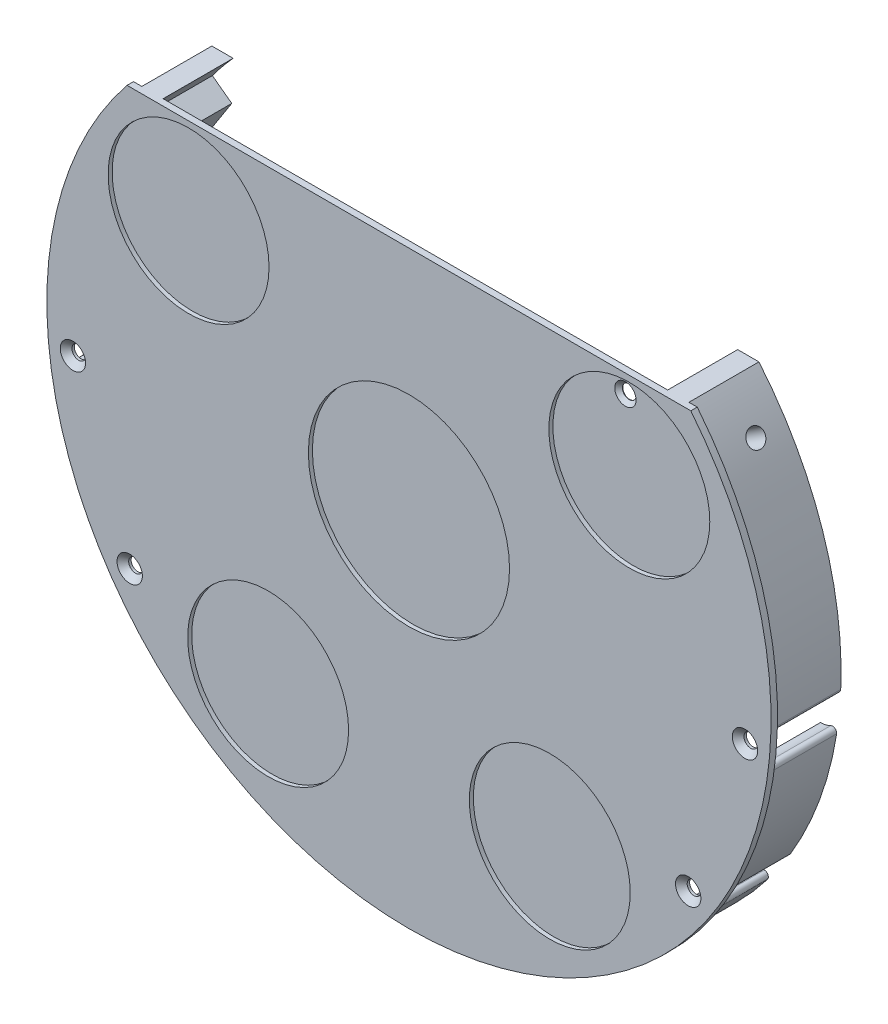
SolidWorks part; units mm, degrees
ref_plane "Front Plane" through (0, 0, 0) normal (0, 0, 1) x (1, 0, 0)
ref_plane "Top Plane" through (0, 0, 0) normal (0, 1, 0) x (1, 0, 0)
ref_plane "Right Plane" through (0, 0, 0) normal (1, 0, 0) x (0, 0, -1)
sketch "Sketch1" plane through (0, 0, 0) normal (0, 0, 1) x (1, 0, 0)
  line L0 (-70.0553, 56.5) -> (70.0553, 56.5)
  line L1 (-68.1175, 56.5) -> (68.1175, 56.5)
  arc A0 (70.0553, 56.5) -> (-70.0553, 56.5) centre (0, 0) cw
  circle A1 centre (52.8, 51) radius 1.7 construction
  circle A2 centre (-69.4053, -47.2163) radius 1.7 construction
  circle A3 centre (-83.5176, -8.4431) radius 1.7 construction
  circle A4 centre (69.4053, -47.2163) radius 1.7 construction
  circle A5 centre (83.5176, -8.4431) radius 1.7 construction
  arc A6 (68.1175, 56.5) -> (-68.1175, 56.5) centre (0, 0) cw construction
  circle A7 centre (-83.5176, -8.4431) radius 1.7
  circle A8 centre (-69.4053, -47.2163) radius 1.7
  circle A9 centre (52.8, 51) radius 1.7
  circle A10 centre (83.5176, -8.4431) radius 1.7
  circle A11 centre (69.4053, -47.2163) radius 1.7
  point P20 (-83.5176, -8.4431)
  point P21 (-69.4053, -47.2163)
  point P22 (52.8, 51)
  point P23 (83.5176, -8.4431)
  point P24 (69.4053, -47.2163)
  point P25 (0, 56.5)
  dimension "D2" = 90
  dimension "D3" = 88.5
  dimension "D15" = 3.4
  dimension "D1" = 140.1107
  dimension "D4" = 136.2351
  dimension "D5" = 64.9431
  dimension "D6" = 105.796
  dimension "D7" = 103.7163
  dimension "D8" = 124.7965
  dimension "D9" = 124.7965
  dimension "D10" = 103.7163
  dimension "D11" = 105.796
  dimension "D12" = 64.9431
  dimension "D13" = 53.0857
  dimension "D14" = 5.5
extrude "Boss-Extrude1" add sketch "Sketch1" along normal blind 2 contours A0 L0 A11 A10 A9 A8 A7 region at (-0.0217, -10.331, 0)
sketch "Sketch3" plane through (0, 0, 2) normal (0, 0, 1) x (1, 0, 0)
  line L0 (-70.0553, 56.5) -> (70.0553, 56.5)
  arc A0 (70.0553, 56.5) -> (-70.0553, 56.5) centre (0, 0) cw
  circle A1 centre (-54.772, 35) radius 20
  circle A2 centre (0, 0) radius 25
  circle A3 centre (54.7723, 35) radius 20
  circle A4 centre (35.0004, -54.772) radius 20
  circle A5 centre (-35, -54.7723) radius 20
  circle M3 centre (52.8, 51) radius 1.7
  dimension "D1" = 90
  dimension "D2" = 40
  dimension "D3" = 50
extrude "Cut-Extrude1" cut sketch "Sketch3" against normal blind 0.5 contours A1 | A5 | A2 | A4 | A3 M3 region at (-54.772, 35, 2) region at (0, 0, 2) region at (54.7866, 34.8836, 2) region at (35.0004, -54.772, 2) region at (-35, -54.7723, 2)
sketch "Sketch4" plane through (0, 0, 0) normal (0, 0, -1) x (-1, 0, 0)
  circle A0 centre (-52.8, 51) radius 3
  circle A1 centre (-83.5176, -8.4431) radius 3
  circle A2 centre (-69.4053, -47.2163) radius 3
  circle A3 centre (69.4053, -47.2163) radius 3
  circle A4 centre (83.5176, -8.4431) radius 3
  arc M6 (-70.0553, 56.5) -> (70.0553, 56.5) centre (0, 0) ccw
  line M7 (70.0553, 56.5) -> (-70.0553, 56.5)
  dimension "D1" = 6
  dimension "D2" = 6
extrude "Boss-Extrude2" add sketch "Sketch4" along normal blind 2 contours A4 A3 A2 A1 A0 M7 M6 region at (-0.0677, -10.3234, 0)
sketch "Sketch5" plane through (0, 0, -2) normal (0, 0, -1) x (-1, 0, 0)
  line L0 (70.0553, 56.5) -> (-70.0553, 56.5) construction
  line L1 (-67.9876, 56.5) -> (-62.6986, 56.5)
  line L2 (62.6986, 56.5) -> (67.9876, 56.5)
  line L3 (0, 0) -> (0, 20.6116) construction
  arc A0 (-67.9876, 56.5) -> (67.9876, 56.5) centre (0, 0) ccw
  arc A1 (-62.6986, 56.5) -> (62.6986, 56.5) centre (0, 0) ccw
  arc A2 (-88.1552, -6.5742) -> (-84.327, -3.5091) centre (-83.5176, -8.4431) cw
  arc A3 (-87.6873, -11.2023) -> (-83.3231, -13.4393) centre (-83.5176, -8.4431) ccw
  arc A4 (-74.3731, -47.7828) -> (-72.4679, -43.264) centre (-69.4053, -47.2163) cw
  arc A5 (-71.7566, -51.6289) -> (-66.8538, -51.5163) centre (-69.4053, -47.2163) ccw
  arc A6 (88.1552, -6.5742) -> (84.327, -3.5091) centre (83.5176, -8.4431) ccw
  arc A7 (71.7566, -51.6289) -> (66.8538, -51.5163) centre (69.4053, -47.2163) cw
  arc A8 (74.3731, -47.7828) -> (72.4679, -43.264) centre (69.4053, -47.2163) ccw
  arc A9 (87.6873, -11.2023) -> (83.3231, -13.4393) centre (83.5176, -8.4431) cw
  line M8 (70.0553, 56.5) -> (-70.0553, 56.5)
  dimension "D2" = 5
  dimension "D3" = 5
  dimension "D4" = 5
  dimension "D5" = 5
  dimension "D1" = 88.4
  dimension "D6" = 84.4
extrude "Boss-Extrude3" add sketch "Sketch5" along normal blind 15 contours A0 A2 A1 M8 | A0 A4 A1 A3 | A0 L3 A1 A5 | L3 A0 A7 A1 | A0 A9 A1 A8 | A6 A0 A1 M8 region at (65.3431, 55.8189, -2) region at (-65.3431, 55.8189, -2) region at (80.7079, -29.3753, -2) region at (-80.7079, -29.3753, -2) region at (69.2564, -53.6963, -2)
fillet "Fillet1" radius 1 8 edges at (-88.1552, -6.5742, -9.5) (-87.6873, -11.2023, -9.5) (-74.3731, -47.7828, -9.5) (-71.7566, -51.6289, -9.5) (74.3731, -47.7828, -9.5) (71.7566, -51.6289, -9.5) (88.1552, -6.5742, -9.5) (87.6873, -11.2023, -9.5)
sketch "Sketch6" plane through (0, 0, -17) normal (0, 0, -1) x (-1, 0, 0)
  line L0 (-71.0732, 52.5657) -> (-63.0333, 46.6194)
  line L1 (-77.3412, 42.8124) -> (-69.3012, 36.866)
  line L2 (-69.3012, 36.866) -> (-63.0333, 46.6194)
  line L3 (-77.3412, 42.8124) -> (-71.0732, 52.5657) construction
  line L4 (0, 56.5) -> (0, 0) construction
  line L5 (62.6986, 56.5) -> (-62.6986, 56.5) construction
  line L6 (69.3012, 36.866) -> (63.0333, 46.6194)
  line L7 (77.3412, 42.8124) -> (69.3012, 36.866)
  line L8 (71.0732, 52.5657) -> (63.0333, 46.6194)
  arc A0 (-67.9876, 56.5) -> (-71.0732, 52.5657) centre (0, 0) ccw
  arc A1 (-71.0732, 52.5657) -> (-77.3412, 42.8124) centre (0, 0) ccw
  arc A2 (71.0732, 52.5657) -> (77.3412, 42.8124) centre (0, 0) cw
  point P7 (-74.3673, 47.7919)
  arc M9 (-84.327, -3.5091) -> (-62.6986, 56.5) centre (0, 0) cw
  dimension "D1" = 5
  dimension "D2" = 5.8
  dimension "D3" = 10
extrude "Boss-Extrude4" add sketch "Sketch6" against normal up to surface (15 mm away) contours L1 L2 L0 M9 | A2 L8 L6 L7 region at (68.6227, 43.5657, -17) region at (-70.2385, 44.7537, -17) up to face at (49.8, 51, -2)
sketch "Sketch7" plane through (-65.8127, 42.2943, 0) normal (0.8413, -0.5406, 0) x (0, 0, -1)
  line L0 (17, -6.4526) -> (17, 5.1411) construction
  line L1 (2, 5.1411) -> (17, 5.1411) construction
  circle A0 centre (9.5, -0.6558) radius 2.2
  point P2 (17, -0.6558)
  point P3 (9.5, 5.1411)
  dimension "D1" = 4.4
extrude "Cut-Extrude2" cut sketch "Sketch7" against normal through all
ref_axis "Axis1" through (0, 56.5, 2) along (0, -1, 0)
ref_plane "Plane2" through (0, 0, 0) normal (1, 0, 0) x (0, -1, 0)
mirror "Mirror1" about plane through (0, 0, 0) normal (1, 0, 0) of "Cut-Extrude2"
hole_wizard "CSK for M3 Flat Head Machine Screw1" positions "3DSketch2" profile "Sketch9" countersink size "M3" standard "ANSI Metric" end condition through all
sketch3d "3DSketch2"
  line L0 (83.5176, -8.4431, 2) -> (83.5176, -8.4431, 0) construction
  line L1 (52.8, 51, 1.5) -> (52.8, 51, 0) construction
  line L2 (69.4053, -47.2163, 2) -> (69.4053, -47.2163, 0) construction
  line L3 (-69.4053, -47.2163, 2) -> (-69.4053, -47.2163, 0) construction
  line L4 (-83.5176, -8.4431, 2) -> (-83.5176, -8.4431, 0) construction
  point P0 (83.5176, -8.4431, 2)
  point P4 (52.8, 51, 1.5)
  point P8 (69.4053, -47.2163, 2)
  point P12 (-69.4053, -47.2163, 2)
  point P16 (-83.5176, -8.4431, 2)
sketch "Sketch9" plane through (83.5176, -8.4431, 2) normal (1, 0, 0) x (0, -1, 0)
  line L0 (0, 0) -> (0, 19)
  line L1 (0, 19) -> (1.7, 19)
  line L2 (1.7, 19) -> (1.7, 1.45)
  line L3 (1.7, 1.45) -> (3.15, 0)
  line L5 (3.15, 0) -> (0, 0)
  line L6 (-1.7, 1.45) -> (-3.15, 0) construction
  line L11 (0, -6.35) -> (0, 107.95) construction
  dimension "Thru Hole Dia." = 3.4
  dimension "Thru Hole Depth" = 19
  dimension "Near C'Sink Dia." = 6.3
  dimension "Near C'Sink Angle" = 90
sketch "Sketch10" plane through (0, 0, 0) normal (0, 0, -1) x (-1, 0, 0)
  circle A0 centre (-83.5176, -8.4431) radius 1.7
  circle A1 centre (-83.5176, -8.4431) radius 3
  circle A2 centre (-69.4053, -47.2163) radius 1.7
  circle A3 centre (-69.4053, -47.2163) radius 3
  circle A4 centre (69.4053, -47.2163) radius 1.7
  circle A5 centre (69.4053, -47.2163) radius 3
  circle A6 centre (83.5176, -8.4431) radius 1.7
  circle A7 centre (83.5176, -8.4431) radius 3
  circle A8 centre (-52.8, 51) radius 1.7
  circle A9 centre (-52.8, 51) radius 3
extrude "Boss-Extrude5" add sketch "Sketch10" along normal blind 0.3
ref_plane "Plane1" through (0, -88.4, 0) normal (0, -1, 0) x (-1, 0, 0)
sketch "Sketch11" plane through (0, -88.4, 0) normal (0, -1, 0) x (-1, 0, 0)
  line L0 (0, 2) -> (0, 17) construction
  line L1 (90, 2) -> (-90, 2) construction
  line L2 (70.1246, 17) -> (-70.1246, 17) construction
  circle A0 centre (0, 9.5) radius 2.5
  point P6 (0, 9.5)
  dimension "D1" = 5
extrude "Boss-Extrude6" add sketch "Sketch11" along normal blind 5 separate body
sketch "Sketch12" plane through (0, 0, -2) normal (0, 0, -1) x (-1, 0, 0)
  line L0 (-2.5, -88.4) -> (-2.5, -93.4) construction
  line L1 (2.5, -93.4) -> (2.5, -88.4) construction
  line L2 (-2.5, -89.9653) -> (-4.5409, -95.2024)
  line L3 (-4.5409, -95.2024) -> (4.0078, -95.2024)
  line L4 (4.0078, -95.2024) -> (2.5, -89.9653)
  arc A0 (-2.5, -89.9653) -> (2.5, -89.9653) centre (0, 0) ccw
  arc A1 (-70.0553, 56.5) -> (70.0553, 56.5) centre (0, 0) ccw construction
extrude "Cut-Extrude3" cut sketch "Sketch12" along normal through all
sketch "Sketch14" plane through (0, 0, 1.5) normal (0, 0, 1) x (1, 0, 0)
  circle A0 centre (-54.772, 35) radius 20
  circle A1 centre (54.7723, 35) radius 20
  circle A2 centre (35.0004, -54.772) radius 20
  circle A3 centre (-35, -54.7723) radius 20
  circle A4 centre (0, 0) radius 25
extrude "Cut-Extrude8" cut sketch "Sketch14" against normal blind 0.5
sketch "Sketch17" plane through (0, 0, -2) normal (0, 0, -1) x (-1, 0, 0)
  line L0 (-86.6841, -4.5736) -> (-85.5756, -3.8863)
  line L1 (-85.5756, -3.8863) -> (-84.327, -3.5091)
  line L2 (-67.8573, 50.1872) -> (-63.0333, 46.6194)
  line L3 (-63.0333, 46.6194) -> (-69.3012, 36.866)
  line L4 (-69.3012, 36.866) -> (-74.096, 40.4122)
  line L5 (-85.8455, -12.8681) -> (-84.6219, -13.3196)
  line L6 (-84.6219, -13.3196) -> (-83.3231, -13.4393)
  line L7 (-72.4679, -43.264) -> (-73.3858, -44.1905)
  line L8 (-73.3858, -44.1905) -> (-74.033, -45.3229)
  line L9 (-69.3437, -52.2159) -> (-68.0527, -52.0299)
  line L10 (-68.0527, -52.0299) -> (-66.8538, -51.5163)
  line L11 (-67.9876, 56.5) -> (-62.6986, 56.5)
  line L12 (0, 48.62) -> (0, -48.62) construction
  line L13 (67.9876, 56.5) -> (62.6986, 56.5)
  line L14 (68.0527, -52.0299) -> (66.8538, -51.5163)
  line L15 (69.3437, -52.2159) -> (68.0527, -52.0299)
  line L16 (73.3858, -44.1905) -> (74.033, -45.3229)
  line L17 (72.4679, -43.264) -> (73.3858, -44.1905)
  line L18 (84.6219, -13.3196) -> (83.3231, -13.4393)
  line L19 (85.8455, -12.8681) -> (84.6219, -13.3196)
  line L20 (69.3012, 36.866) -> (74.096, 40.4122)
  line L21 (63.0333, 46.6194) -> (69.3012, 36.866)
  line L22 (67.8573, 50.1872) -> (63.0333, 46.6194)
  line L23 (85.5756, -3.8863) -> (84.327, -3.5091)
  line L24 (86.6841, -4.5736) -> (85.5756, -3.8863)
  arc A0 (-67.9876, 56.5) -> (-88.3164, -3.8431) centre (0, 0) ccw
  arc A1 (-88.3164, -3.8431) -> (-86.6841, -4.5736) centre (-87.3174, -3.7996) ccw
  arc A2 (-84.327, -3.5091) -> (-86.6841, -4.5736) centre (-83.5176, -8.4431) ccw construction
  arc A3 (-74.096, 40.4122) -> (-84.327, -3.5091) centre (0, 0) ccw
  arc A5 (-83.3231, -13.4393) -> (-72.4679, -43.264) centre (0, 0) ccw
  arc A6 (-85.8455, -12.8681) -> (-83.3231, -13.4393) centre (-83.5176, -8.4431) ccw construction
  arc A7 (-85.8455, -12.8681) -> (-83.3231, -13.4393) centre (-83.5176, -8.4431) ccw construction
  arc A8 (-83.3231, -13.4393) -> (-72.4679, -43.264) centre (0, 0) ccw construction
  arc A9 (-85.8455, -12.8681) -> (-87.2987, -13.9105) centre (-86.3111, -13.7531) ccw
  arc A10 (-75.8161, -45.4585) -> (-74.033, -45.3229) centre (-74.9585, -44.9442) ccw
  arc A11 (-87.2987, -13.9105) -> (-75.8161, -45.4585) centre (0, 0) ccw
  arc A12 (-72.4679, -43.264) -> (-74.033, -45.3229) centre (-69.4053, -47.2163) ccw construction
  arc A13 (-69.3437, -52.2159) -> (-66.8538, -51.5163) centre (-69.4053, -47.2163) ccw construction
  arc A14 (-66.8538, -51.5163) -> (66.8538, -51.5163) centre (0, 0) ccw
  arc A16 (-69.3437, -52.2159) -> (-70.1246, -53.8247) centre (-69.3313, -53.2158) ccw
  arc A17 (-70.1246, -53.8247) -> (70.1246, -53.8247) centre (0, 0) ccw
  arc A19 (-62.6986, 56.5) -> (-67.8573, 50.1872) centre (0, 0) ccw
  arc A20 (62.6986, 56.5) -> (67.8573, 50.1872) centre (0, 0) cw
  arc A21 (69.3437, -52.2159) -> (70.1246, -53.8247) centre (69.3313, -53.2158) cw
  arc A22 (87.2987, -13.9105) -> (75.8161, -45.4585) centre (0, 0) cw
  arc A23 (75.8161, -45.4585) -> (74.033, -45.3229) centre (74.9585, -44.9442) cw
  arc A24 (85.8455, -12.8681) -> (87.2987, -13.9105) centre (86.3111, -13.7531) cw
  arc A25 (83.3231, -13.4393) -> (72.4679, -43.264) centre (0, 0) cw
  arc A26 (74.096, 40.4122) -> (84.327, -3.5091) centre (0, 0) cw
  arc A27 (88.3164, -3.8431) -> (86.6841, -4.5736) centre (87.3174, -3.7996) cw
  arc A28 (67.9876, 56.5) -> (88.3164, -3.8431) centre (0, 0) cw
  line M1 (-69.3012, 36.866) -> (-74.096, 40.4122)
  arc M2 (-74.096, 40.4122) -> (-84.327, -3.5091) centre (0, 0) ccw
  arc M4 (-86.6841, -4.5736) -> (-88.3164, -3.8431) centre (-87.3174, -3.7996) cw
  arc M5 (-88.3164, -3.8431) -> (-67.9876, 56.5) centre (0, 0) cw
  line M6 (-67.9876, 56.5) -> (-70.0553, 56.5)
  arc M7 (-70.0553, 56.5) -> (70.0553, 56.5) centre (0, 0) ccw
  line M8 (70.0553, 56.5) -> (67.9876, 56.5)
  arc M9 (67.9876, 56.5) -> (88.3164, -3.8431) centre (0, 0) cw
  arc M10 (88.3164, -3.8431) -> (86.6841, -4.5736) centre (87.3174, -3.7996) cw
  arc M12 (84.327, -3.5091) -> (74.096, 40.4122) centre (0, 0) ccw
  line M13 (74.096, 40.4122) -> (69.3012, 36.866)
  line M14 (69.3012, 36.866) -> (63.0333, 46.6194)
  line M15 (63.0333, 46.6194) -> (67.8573, 50.1872)
  arc M16 (67.8573, 50.1872) -> (62.6986, 56.5) centre (0, 0) ccw
  line M17 (62.6986, 56.5) -> (-62.6986, 56.5)
  arc M18 (-62.6986, 56.5) -> (-67.8573, 50.1872) centre (0, 0) ccw
  line M19 (-67.8573, 50.1872) -> (-63.0333, 46.6194)
  line M20 (-63.0333, 46.6194) -> (-69.3012, 36.866)
  circle M21 centre (-52.8, 51) radius 3
  circle M22 centre (-83.5176, -8.4431) radius 3
  circle M23 centre (-69.4053, -47.2163) radius 3
  circle M24 centre (69.4053, -47.2163) radius 3
  circle M25 centre (83.5176, -8.4431) radius 3
  arc M27 (85.8455, -12.8681) -> (87.2987, -13.9105) centre (86.3111, -13.7531) cw
  arc M28 (87.2987, -13.9105) -> (75.8161, -45.4585) centre (0, 0) cw
  arc M29 (75.8161, -45.4585) -> (74.033, -45.3229) centre (74.9585, -44.9442) cw
  arc M31 (72.4679, -43.264) -> (83.3231, -13.4393) centre (0, 0) ccw
  arc M33 (69.3437, -52.2159) -> (70.1246, -53.8247) centre (69.3313, -53.2158) cw
  arc M34 (70.1246, -53.8247) -> (-70.1246, -53.8247) centre (0, 0) cw
  arc M35 (-70.1246, -53.8247) -> (-69.3437, -52.2159) centre (-69.3313, -53.2158) cw
  arc M37 (-66.8538, -51.5163) -> (66.8538, -51.5163) centre (0, 0) ccw
extrude "Cut-Extrude9" cut sketch "Sketch17" against normal blind 2.4 contours L24 L23 L1 L0 L19 L16 L17 L18 L15 L9 L10 L14 M10 M12 M13 M14 M15 M16 M17 M18 M19 M20 M1 M2 M4 M5 M6 M7 M8 M9 M27 M28 M29 M31 M33 M34 M35 M37 M21 M23 M25 M24 M22 region at (-0.073, -9.4118, -2)
sketch "Sketch18" plane through (0, 0, -0.3) normal (0, 0, -1) x (-1, 0, 0)
  circle A0 centre (-83.5176, -8.4431) radius 3
  circle A1 centre (-83.5176, -8.4431) radius 1.7
  circle A2 centre (-52.8, 51) radius 1.7
  circle A3 centre (-52.8, 51) radius 3
  circle A4 centre (83.5176, -8.4431) radius 1.7
  circle A5 centre (83.5176, -8.4431) radius 3
  circle A6 centre (69.4053, -47.2163) radius 1.7
  circle A7 centre (69.4053, -47.2163) radius 3
  circle A8 centre (-69.4053, -47.2163) radius 1.7
  circle A9 centre (-69.4053, -47.2163) radius 3
extrude "Cut-Extrude10" cut sketch "Sketch18" against normal blind 0.25
